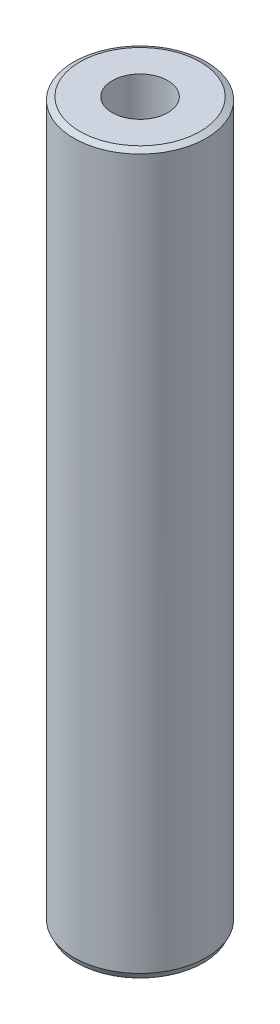
SolidWorks part; units mm, degrees
ref_plane "Front Plane" through (0, 0, 0) normal (0, 0, 1) x (1, 0, 0)
ref_plane "Top Plane" through (0, 0, 0) normal (0, 1, 0) x (1, 0, 0)
ref_plane "Right Plane" through (0, 0, 0) normal (1, 0, 0) x (0, 0, -1)
sketch "Sketch1" plane through (0, 0, 0) normal (0, 1, 0) x (1, 0, 0)
  circle A0 centre (0, 0) radius 5
  dimension "SHAFT_OD" = 10
extrude "Boss-Extrude1" add sketch "Sketch1" along normal blind 54.2338
sketch "Sketch2" plane through (0, 0, 0) normal (0, 1, 0) x (1, 0, 0)
  circle A0 centre (0, 0) radius 2.0989
  dimension "BORE_D" = 4.1977
extrude "Cut-Extrude1" cut sketch "Sketch2" along normal through all
chamfer "Chamfer1" distance 0.2208 angle 64.063 2 edges at (0, 54.2338, 5) (0, 0, 5) first distance on face at (0, 54.2338, 5) first distance on face at (0, 0, 2.0989)
